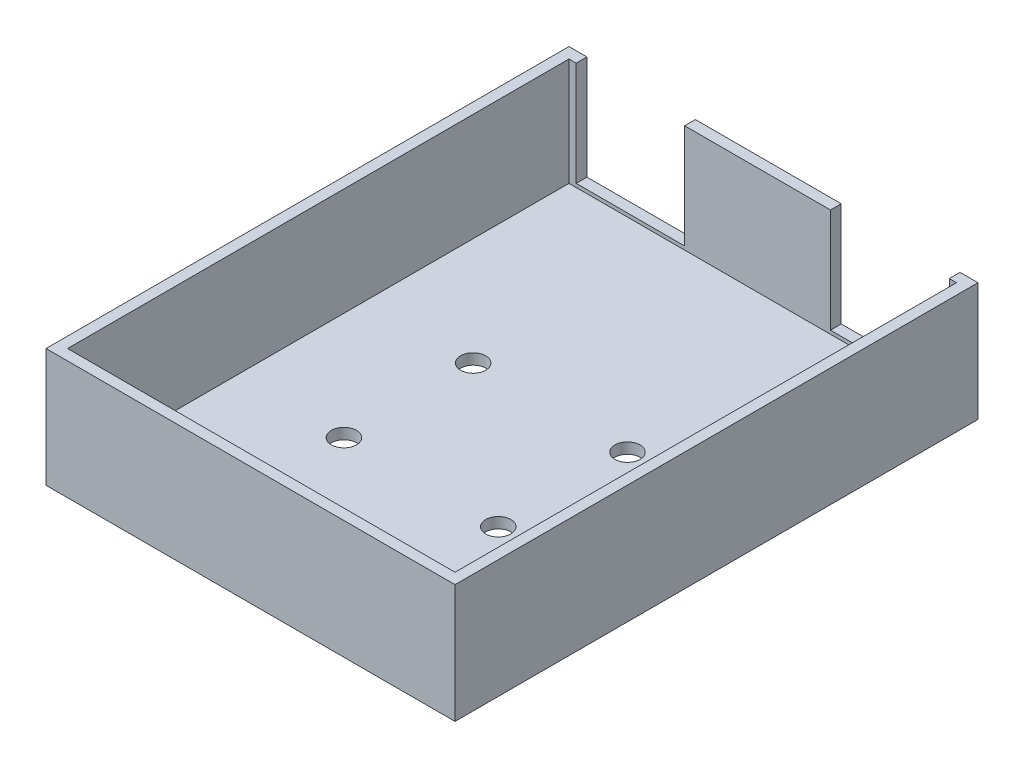
SolidWorks part; units mm, degrees
ref_plane "Front" through (0, 0, 0) normal (0, 0, 1) x (1, 0, 0)
ref_plane "Top" through (0, 0, 0) normal (0, 1, 0) x (1, 0, 0)
ref_plane "Right" through (0, 0, 0) normal (1, 0, 0) x (0, 0, -1)
sketch "Sketch1" plane through (0, 0, 0) normal (0, 1, 0) x (1, 0, 0)
  line L0 (-19.6957, 22.2835) -> (34.2793, 22.2835)
  line L1 (-21.1957, 23.7835) -> (35.7793, 23.7835)
  line L2 (-21.1957, 23.7835) -> (-21.1957, -49.0665)
  line L3 (-21.1957, -49.0665) -> (35.7793, -49.0665)
  line L4 (35.7793, 23.7835) -> (35.7793, -49.0665)
  line L5 (34.2793, 22.2835) -> (34.2793, -47.5665)
  line L6 (-19.6957, -47.5665) -> (34.2793, -47.5665)
  line L7 (-19.6957, 22.2835) -> (-19.6957, -47.5665)
  dimension "D1" = 56.975
  dimension "D2" = 72.85
  dimension "D3" = 1.5
extrude "Boss-Extrude1" add sketch "Sketch1" along normal blind 1.5 contours L0 L5 L6 L7
extrude "Boss-Extrude2" add sketch "Sketch1<4>" along normal blind 16.5
sketch "Sketch1<4>" plane through (0, 0, 0) normal (0, 1, 0) x (1, 0, 0) same geometry as "Sketch1"
sketch "Sketch2" plane through (0, 0, -23.7835) normal (0, 0, -1) x (-1, 0, 0)
  line L0 (-35.7793, 0) -> (21.1957, 0) construction
  line L1 (-35.7793, 16.5) -> (-16.7293, 16.5)
  line L2 (-35.7793, 16.5) -> (-35.7793, 0)
  line L3 (-35.7793, 0) -> (-16.7293, 0)
  line L4 (-16.7293, 16.5) -> (-16.7293, 0)
  line L5 (-33.2793, 16.5) -> (-33.2793, 0)
  line L6 (21.1957, 16.5) -> (3.5907, 16.5)
  line L7 (21.1957, 16.5) -> (21.1957, 0)
  line L8 (21.1957, 0) -> (3.5907, 0)
  line L9 (3.5907, 16.5) -> (3.5907, 0)
  line L10 (18.6957, 16.5) -> (18.6957, 0)
  line L11 (-33.2793, 2) -> (18.6957, 2)
  line M12 (21.1957, 16.5) -> (-35.7793, 16.5)
  dimension "D1" = 20.32
  dimension "D2" = 39.37
  dimension "D3" = 2.5
  dimension "D4" = 2
  dimension "D5" = 2.5
extrude "Cut-Extrude1" cut sketch "Sketch2" against normal up to next contours L5 L11 L4 M12 | L9 L11 L10 L6 region at (25.0043, 9.25, -23.7835) region at (-11.1432, 9.25, -23.7835)
sketch "Sketch3" plane through (0, 0, 0) normal (0, -1, 0) x (1, 0, 0)
  line L0 (-21.1957, 49.0665) -> (35.7793, 49.0665) construction
  line L1 (-21.1957, -23.7835) -> (-21.1957, 49.0665) construction
  circle A0 centre (16.8043, 24.0665) radius 1.75
  circle A1 centre (-4.6957, 24.0665) radius 1.75
  circle A2 centre (16.8043, 6.0665) radius 1.75
  circle A3 centre (-4.6957, 6.0665) radius 1.75
  dimension "D1" = 3.5
  dimension "D3" = 3.5
  dimension "D2" = 25
  dimension "D4" = 21.5
  dimension "D5" = 16.5
  dimension "D6" = 2
extrude "Cut-Extrude2" cut sketch "Sketch3" against normal up to next
